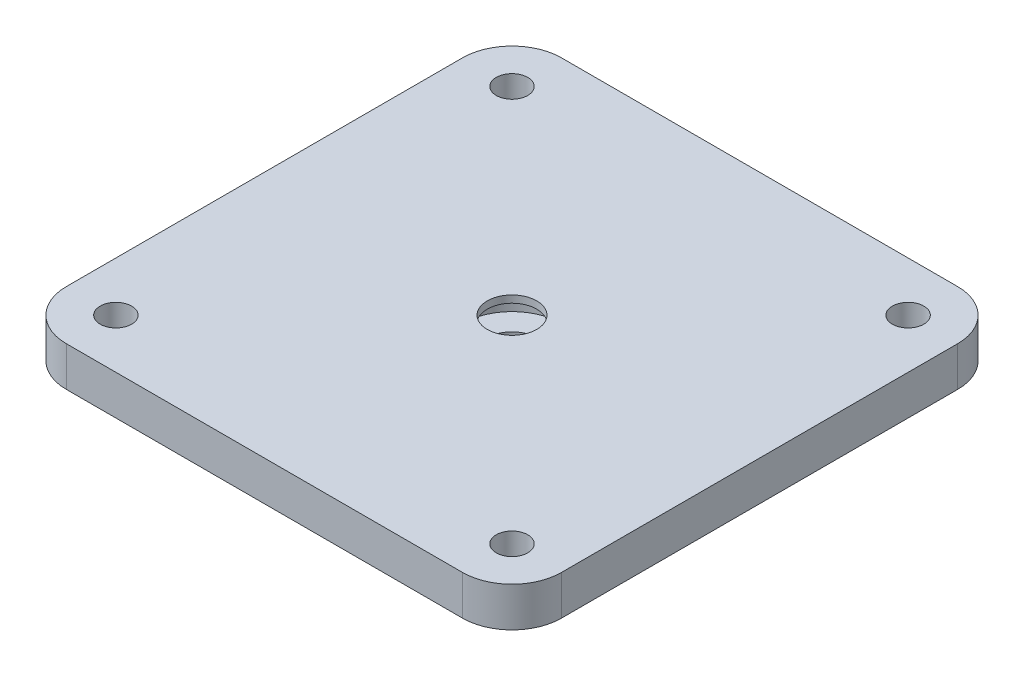
SolidWorks part; units mm, degrees
material "ABS PC"
ref_plane "Front Plane" through (0, 0, 0) normal (0, 0, 1) x (1, 0, 0)
ref_plane "Top Plane" through (0, 0, 0) normal (0, 1, 0) x (1, 0, 0)
ref_plane "Right Plane" through (0, 0, 0) normal (1, 0, 0) x (0, 0, -1)
sketch "Sketch1" plane through (0, 0, 0) normal (0, 1, 0) x (1, 0, 0)
  line L1 (-41.199, 52.7578) -> (38.801, 52.7578)
  line L2 (-51.199, 42.7578) -> (-51.199, -37.2422)
  line L3 (-41.199, -47.2422) -> (38.801, -47.2422)
  line L4 (48.801, 42.7578) -> (48.801, -37.2422)
  arc A0 (-41.199, 52.7578) -> (-51.199, 42.7578) centre (-41.199, 42.7578) ccw
  arc A1 (-51.199, -37.2422) -> (-41.199, -47.2422) centre (-41.199, -37.2422) ccw
  arc A2 (38.801, -47.2422) -> (48.801, -37.2422) centre (38.801, -37.2422) ccw
  arc A3 (48.801, 42.7578) -> (38.801, 52.7578) centre (38.801, 42.7578) ccw
  circle A4 centre (0, 0) radius 6.35
  circle A5 centre (0, 0) radius 12.7
  circle A6 centre (-41.199, 42.7578) radius 3.175
  circle A7 centre (38.801, 42.7578) radius 3.175
  circle A8 centre (38.801, -37.2422) radius 3.175
  circle A9 centre (-41.199, -37.2422) radius 3.175
  point P6 (-51.199, 52.7578)
  point P9 (-51.199, -47.2422)
  point P14 (48.801, 52.7578)
  dimension "D3" = 10
  dimension "D4" = 12.7
  dimension "D5" = 25.4
  dimension "D6" = 6.35
  dimension "D7" = 6.35
  dimension "D8" = 6.35
  dimension "D9" = 6.35
  dimension "D1" = 100
  dimension "D2" = 100
extrude "Boss-Extrude1" add sketch "Sketch1" along normal blind 10 contours L4 A3 L1 A0 L2 A1 L3 A2 A5 region at (-1.199, 0, -51.3436)
extrude "Boss-Extrude2" add sketch "Sketch1<3>" along normal blind 2.5 contours A5 A4 region at (-12.3408, 0, 0)
sketch "Sketch1<3>" plane through (0, 0, 0) normal (0, 1, 0) x (1, 0, 0) same geometry as "Sketch1"
sketch "Sketch2" plane through (0, 10, 0) normal (0, 1, 0) x (1, 0, 0)
  line L4 (48.801, -37.2422) -> (48.801, 42.7578)
  line L5 (38.801, 52.7578) -> (-41.199, 52.7578)
  line L6 (-51.199, 42.7578) -> (-51.199, -37.2422)
  line L7 (-41.199, -47.2422) -> (38.801, -47.2422)
  line L8 (48.801, -37.2422) -> (48.801, 42.7578)
  line L9 (38.801, 52.7578) -> (-41.199, 52.7578)
  line L10 (-51.199, 42.7578) -> (-51.199, -37.2422)
  line L11 (-41.199, -47.2422) -> (38.801, -47.2422)
  circle A0 centre (0, 0) radius 12.7
  circle A1 centre (0, 0) radius 12.7 construction
  arc A4 (48.801, 42.7578) -> (38.801, 52.7578) centre (38.801, 42.7578) ccw
  arc A5 (-41.199, 52.7578) -> (-51.199, 42.7578) centre (-41.199, 42.7578) ccw
  arc A6 (-51.199, -37.2422) -> (-41.199, -47.2422) centre (-41.199, -37.2422) ccw
  arc A7 (38.801, -47.2422) -> (48.801, -37.2422) centre (38.801, -37.2422) ccw
  arc A8 (48.801, 42.7578) -> (38.801, 52.7578) centre (38.801, 42.7578) ccw
  arc A9 (-41.199, 52.7578) -> (-51.199, 42.7578) centre (-41.199, 42.7578) ccw
  arc A10 (-51.199, -37.2422) -> (-41.199, -47.2422) centre (-41.199, -37.2422) ccw
  arc A11 (38.801, -47.2422) -> (48.801, -37.2422) centre (38.801, -37.2422) ccw
  dimension "D1" = 0
extrude "Boss-Extrude3" add sketch "Sketch2" against normal through all contours A0
sketch "Sketch3" plane through (0, 10, 0) normal (0, 1, 0) x (1, 0, 0)
  line L0 (-51.199, 2.7578) -> (3.0728, 2.7578) construction
  line L1 (-1.199, 52.7578) -> (-1.199, 2.7578) construction
  line L4 (48.801, -37.2422) -> (48.801, 42.7578)
  line L5 (38.801, 52.7578) -> (-41.199, 52.7578)
  line L6 (-51.199, 42.7578) -> (-51.199, -37.2422)
  line L7 (-41.199, -47.2422) -> (38.801, -47.2422)
  line L8 (48.801, -37.2422) -> (48.801, 42.7578)
  line L9 (38.801, 52.7578) -> (-41.199, 52.7578)
  line L10 (-51.199, 42.7578) -> (-51.199, -37.2422)
  line L11 (-41.199, -47.2422) -> (38.801, -47.2422)
  circle A1 centre (-1.199, 2.7578) radius 5
  arc A4 (48.801, 42.7578) -> (38.801, 52.7578) centre (38.801, 42.7578) ccw
  arc A5 (-41.199, 52.7578) -> (-51.199, 42.7578) centre (-41.199, 42.7578) ccw
  arc A6 (-51.199, -37.2422) -> (-41.199, -47.2422) centre (-41.199, -37.2422) ccw
  arc A7 (38.801, -47.2422) -> (48.801, -37.2422) centre (38.801, -37.2422) ccw
  arc A8 (48.801, 42.7578) -> (38.801, 52.7578) centre (38.801, 42.7578) ccw
  arc A9 (-41.199, 52.7578) -> (-51.199, 42.7578) centre (-41.199, 42.7578) ccw
  arc A10 (-51.199, -37.2422) -> (-41.199, -47.2422) centre (-41.199, -37.2422) ccw
  arc A11 (38.801, -47.2422) -> (48.801, -37.2422) centre (38.801, -37.2422) ccw
  dimension "D2" = 10
  dimension "D1" = 0
extrude "Cut-Extrude3" cut sketch "Sketch3" against normal blind 10 contours A1
sketch "Sketch4" plane through (0, 10, 0) normal (0, 1, 0) x (1, 0, 0)
  circle A1 centre (-1.199, 2.7578) radius 10
  dimension "D1" = 20
extrude "Cut-Extrude4" cut sketch "Sketch4" against normal blind 5 from offset 1.45 offset against normal yes
sketch "Sketch6" plane through (0, 0, 0) normal (0, -1, 0) x (1, 0, 0)
  line L4 (48.801, -42.7578) -> (48.801, 37.2422)
  line L5 (38.801, 47.2422) -> (-41.199, 47.2422)
  line L6 (-51.199, 37.2422) -> (-51.199, -42.7578)
  line L7 (-41.199, -52.7578) -> (38.801, -52.7578)
  line L8 (48.801, -42.7578) -> (48.801, 37.2422)
  line L9 (38.801, 47.2422) -> (-41.199, 47.2422)
  line L10 (-51.199, 37.2422) -> (-51.199, -42.7578)
  line L11 (-41.199, -52.7578) -> (38.801, -52.7578)
  arc A4 (48.801, 37.2422) -> (38.801, 47.2422) centre (38.801, 37.2422) ccw
  arc A5 (-41.199, 47.2422) -> (-51.199, 37.2422) centre (-41.199, 37.2422) ccw
  arc A6 (-51.199, -42.7578) -> (-41.199, -52.7578) centre (-41.199, -42.7578) ccw
  arc A7 (38.801, -52.7578) -> (48.801, -42.7578) centre (38.801, -42.7578) ccw
  arc A8 (48.801, 37.2422) -> (38.801, 47.2422) centre (38.801, 37.2422) ccw
  arc A9 (-41.199, 47.2422) -> (-51.199, 37.2422) centre (-41.199, 37.2422) ccw
  arc A10 (-51.199, -42.7578) -> (-41.199, -52.7578) centre (-41.199, -42.7578) ccw
  arc A11 (38.801, -52.7578) -> (48.801, -42.7578) centre (38.801, -42.7578) ccw
  dimension "D1" = 0
extrude "Cut-Extrude5" cut sketch "Sketch6" against normal blind 2
